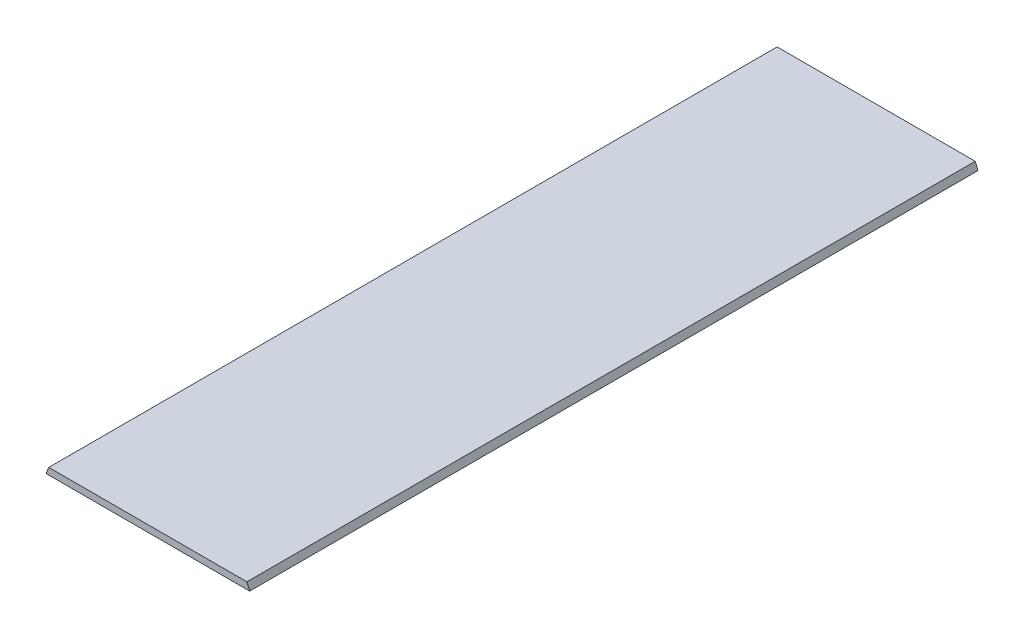
SolidWorks part; units mm, degrees
ref_plane "Front Plane" through (0, 0, 0) normal (0, 0, 1) x (1, 0, 0)
ref_plane "Top Plane" through (0, 0, 0) normal (0, 1, 0) x (1, 0, 0)
ref_plane "Right Plane" through (0, 0, 0) normal (1, 0, 0) x (0, 0, -1)
sketch "Sketch1" plane through (0, 0, 0) normal (0, 0, 1) x (1, 0, 0)
  line L0 (0, 0) -> (2.6303, 6.35)
  line L1 (2.6303, 6.35) -> (190.9177, 6.35)
  line L2 (190.9177, 6.35) -> (193.548, 0)
  line L3 (193.548, 0) -> (0, 0)
  dimension "D1" = 6.35
  dimension "D2" = 67.5
  dimension "D3" = 67.5
  dimension "D4" = 193.548
extrude "Boss-Extrude1" add sketch "Sketch1" along normal blind 692.15
